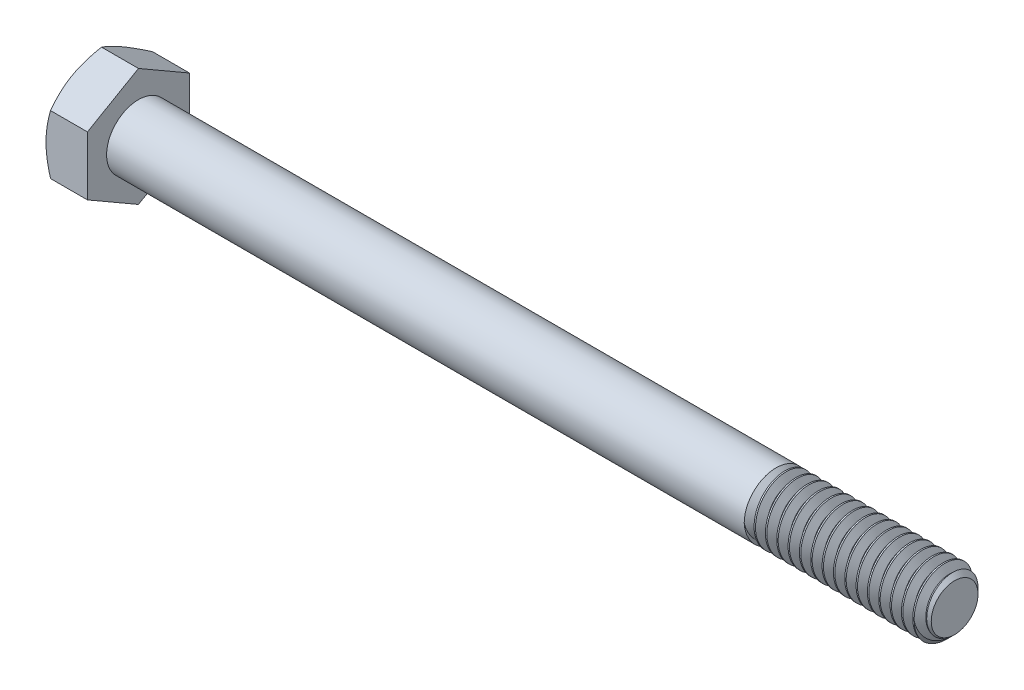
SolidWorks part; units mm, degrees
ref_plane "Front Plane" through (0, 0, 0) normal (0, 0, 1) x (1, 0, 0)
ref_plane "Top Plane" through (0, 0, 0) normal (0, 1, 0) x (1, 0, 0)
ref_plane "Right Plane" through (0, 0, 0) normal (1, 0, 0) x (0, 0, -1)
sketch "Sketch1" plane through (0, 0, 0) normal (0, 0, 1) x (1, 0, 0)
  line L0 (-53.3797, 0) -> (53.3797, 0) construction
  line L1 (53.3797, 3.9688) -> (53.3797, -3.9688) construction
  line L2 (-48.2203, 6.35) -> (-48.2203, -6.35) construction
  line L3 (-53.3797, 6.35) -> (-53.3797, -6.35) construction
  point P9 (-48.2203, 0)
  point P10 (48.4408, -3.9688)
  dimension "Screw Dia" = 7.9375
  dimension "Hex" = 12.7
  dimension "Head Ht" = 5.1594
  dimension "Screw Lenght" = 101.6
  dimension "D1" = 4.9389
ref_plane "Plane2" through (53.3797, 0, 0) normal (1, 0, 0) x (0, 0, -1)
sketch "Sketch5" plane through (53.3797, 0, 0) normal (1, 0, 0) x (0, 0, -1)
  circle A0 centre (0, 0) radius 3.9688
extrude "Boss-Extrude3" add sketch "Sketch5" against normal up to vertex (101.6 mm away) up to point (-48.2203, 0, 0)
sketch "Sketch9" plane through (53.3797, 0, 0) normal (1, 0, 0) x (0, 0, -1)
  circle A1 centre (0, 0) radius 3.9688
  circle A2 centre (0, 0) radius 3.9688
  dimension "D1" = 0
curve "Helix/Spiral1" pitch 1.4111 height 23.6361 turns 16.75 parameters "Pitch"=1.4111
chamfer "Chamfer1" distance 1.0583 angle 45 1 edges at (53.3797, 0, -3.9688)
sketch "Sketch10" plane through (0, 0, 0) normal (0, 0, 1) x (1, 0, 0)
  line L0 (53.3797, 3.9688) -> (53.9089, 3.0522)
  line L1 (53.9089, 3.0522) -> (54.0852, 3.0522)
  line L2 (54.0852, 3.0522) -> (54.6144, 3.9687)
  line L3 (53.3797, 3.9688) -> (54.6144, 3.9687)
  line L4 (53.997, 3.9688) -> (53.997, 3.0522) construction
  line L5 (53.6443, 3.5105) -> (54.3498, 3.5105) construction
  dimension "D1" = 60
  dimension "D2" = 0.1764
  dimension "D3" = 0.7056
sweep "Cut-Sweep1" cut profiles "Sketch10" path "Helix/Spiral1" align with end faces yes
sketch "Sketch11" plane through (0, 0, 0) normal (0, 0, 1) x (1, 0, 0)
  line L0 (-48.2203, 3.9688) -> (-48.2203, 0)
  line L1 (-48.2203, 0) -> (35.1234, 0)
  line L3 (35.1234, 0) -> (31.1547, 3.9688)
  line L4 (-48.2203, 3.9688) -> (31.1547, 3.9688)
  dimension "D1" = 45
  dimension "MIn Thread" = 22.225
revolve "Revolve1" add sketch "Sketch11" angle 360 about L1
sketch "Sketch6" plane through (-48.2203, 0, 0) normal (-1, 0, 0) x (0, 0, 1)
  line L0 (0, 6.35) -> (0, -6.35) construction
  line L1 (6.35, 3.6662) -> (0, 7.3323)
  line L2 (0, 7.3323) -> (-6.35, 3.6662)
  line L3 (-6.35, 3.6662) -> (-6.35, -3.6662)
  line L4 (-6.35, -3.6662) -> (0, -7.3323)
  line L5 (0, -7.3323) -> (6.35, -3.6662)
  line L6 (6.35, -3.6662) -> (6.35, 3.6662)
  circle A0 centre (0, 0) radius 6.35 construction
extrude "Boss-Extrude4" add sketch "Sketch6" along normal up to vertex (5.1594 mm away) up to point (-53.3797, -6.35, 0)
sketch "Sketch7" plane through (-53.3797, 0, 0) normal (-1, 0, 0) x (0, 0, 1)
  circle A0 centre (0, 0) radius 6.35 construction
  circle A1 centre (0, 0) radius 6.35
sketch "Sketch8" plane through (-53.3797, 0, 0) normal (-1, 0, 0) x (0, 0, 1)
  circle A0 centre (0, 0) radius 6.35 construction
  circle A1 centre (0, 0) radius 6.35
extrude "Cut-Extrude3" cut sketch "Sketch8" against normal through all draft 60 flip side to cut
sketch "Sketch12" plane through (-53.3797, 0, 0) normal (-1, 0, 0) x (0, 0, 1)
  line L0 (0, 4.8895) -> (0, 2.7305) construction
  line L1 (0.1905, 4.8895) -> (0.1905, 2.7305)
  line L2 (-0.1905, 4.8895) -> (-0.1905, 2.7305)
  line L3 (0, 3.9688) -> (0, -3.9688) construction
  arc A0 (0.1905, 4.8895) -> (-0.1905, 4.8895) centre (0, 4.8895) ccw
  arc A1 (-0.1905, 2.7305) -> (0.1905, 2.7305) centre (0, 2.7305) ccw
  circle A3 centre (0, 0) radius 2.54 construction
  circle A4 centre (0, 0) radius 5.08 construction
  point P2 (0, 3.81)
  dimension "D1" = 5.08
  dimension "D3" = 10.16
  dimension "D2" = 0.381
extrude "Cut-Extrude4" cut sketch "Sketch12" against normal blind 0.254
pattern_circular "CirPattern1" count 3 over 360 about axis through (0, 0, 0) along (1, 0, 0) of "Cut-Extrude4"
equation "\"D2@Sketch10\" = \"Pitch@Helix/Spiral1\"*.125"
equation "\"D3@Sketch10\" = \"Pitch@Helix/Spiral1\"*.5"
equation "\"D3@Helix/Spiral1\" = \"MIn Thread@Sketch11\"+\"Pitch@Helix/Spiral1\""
equation "\"D1@Chamfer1\" = \"Pitch@Helix/Spiral1\"*.75"
equation "\"D1@Sketch12\" = \"Hex@Sketch1\"*.4"
equation "\"D3@Sketch12\" = \"Hex@Sketch1\"*.8"
equation "\"D2@Sketch12\" = \"Hex@Sketch1\"*.03"
equation "\"D1@Sketch1\" = \"Pitch@Helix/Spiral1\"*3.5"
